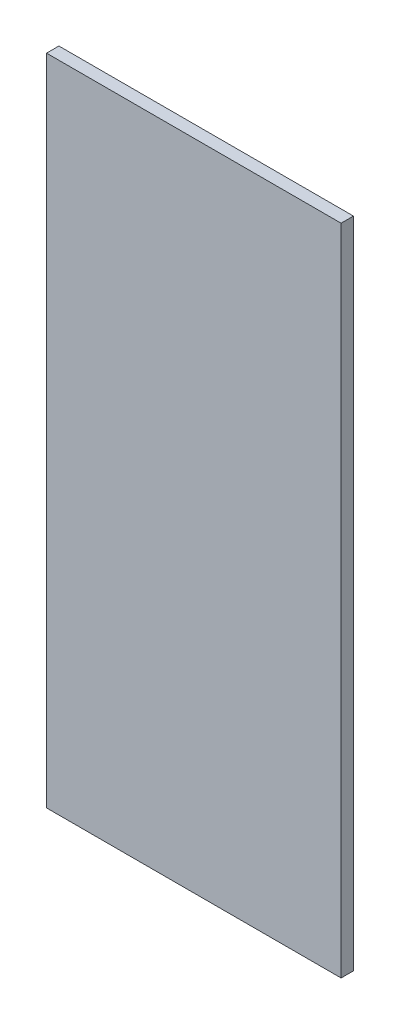
SolidWorks part; units mm, degrees
material "Perspex (TM) GS Acrylic Cast Sheet"
ref_plane "Front Plane" through (0, 0, 0) normal (0, 0, 1) x (1, 0, 0)
ref_plane "Top Plane" through (0, 0, 0) normal (0, 1, 0) x (1, 0, 0)
ref_plane "Right Plane" through (0, 0, 0) normal (1, 0, 0) x (0, 0, -1)
sketch "Sketch1" plane through (0, 0, 0) normal (0, 0, 1) x (1, 0, 0)
  line L1 (-71.5, -158.685) -> (71.5, -158.685)
  line L2 (-71.5, -158.685) -> (-71.5, 158.685)
  line L3 (-71.5, 158.685) -> (71.5, 158.685)
  line L4 (71.5, -158.685) -> (71.5, 158.685)
  line L5 (-71.5, -158.685) -> (71.5, 158.685) construction
  line L6 (-71.5, 158.685) -> (71.5, -158.685) construction
  point P0 (0, 0)
  dimension "D1" = 143
  dimension "D2" = 317.37
extrude "Boss-Extrude1" add sketch "Sketch1" along normal blind 6
equation "\"PCLength\"= 143mm'Length across I/O from PS to GPU"
equation "\"PCWidth\"= 340mm'Distance of longest part parallel to GPU(ussually GPU)"
equation "\"PCHeight\"= 190mm'Tallest point with mobo laying flat"
equation "\"WallThickness\"= 9mm'Thickness of each outer tank wall"
equation "\"ThermoBarrierThickness\"= 6mm'Thickness of barrier between hot side and cold side"
equation "\"HotSideGap\"= 15mm'Space in the hot side that hot fluid flows into"
equation "\"PCClearance\"= 40mm'Clearance from top of tank to top of PC"
equation "\"RadiatorHeight\"= 277.37mm'Final Height from ground of radiators"
equation "\"D1@Sketch1\"=\"PCLength\""
equation "\"D2@Sketch1\"=\"RadiatorHeight\" + 40"
equation "\"D1@Boss-Extrude1\"=\"ThermoBarrierThickness\""
